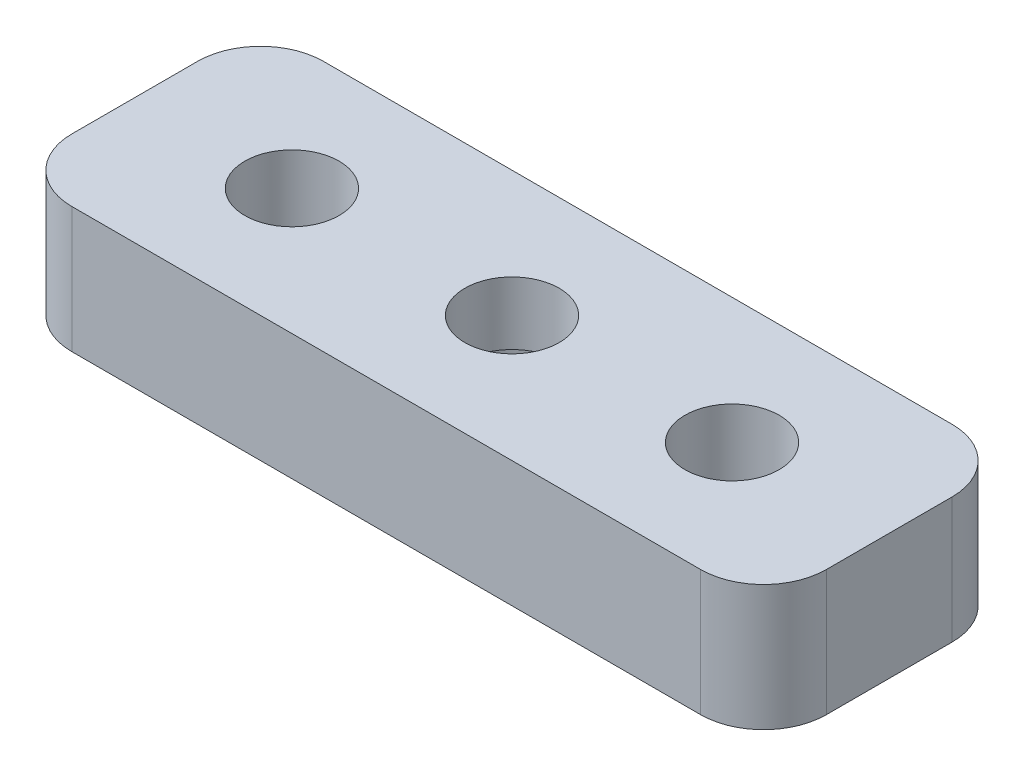
SolidWorks part; units mm, degrees
ref_plane "Front Plane" through (0, 0, 0) normal (0, 0, 1) x (1, 0, 0)
ref_plane "Top Plane" through (0, 0, 0) normal (0, 1, 0) x (1, 0, 0)
ref_plane "Right Plane" through (0, 0, 0) normal (1, 0, 0) x (0, 0, -1)
sketch "Sketch1" plane through (0, 0, 0) normal (0, 1, 0) x (1, 0, 0)
  line L0 (0, 4) -> (10, 4)
  line L1 (12, 2) -> (12, -2)
  line L2 (10, -4) -> (0, -4)
  line L3 (0, -4) -> (-10, -4)
  line L4 (-12, -2) -> (-12, 2)
  line L5 (-10, 4) -> (0, 4)
  line L6 (0, -2.2) -> (0, 2.2) construction
  circle A0 centre (0, 0) radius 4 construction
  circle A1 centre (0, 0) radius 1.5
  arc A2 (10, -4) -> (12, -2) centre (10, -2) ccw
  arc A3 (12, 2) -> (10, 4) centre (10, 2) ccw
  arc A4 (-10, -4) -> (-12, -2) centre (-10, -2) cw
  arc A5 (-10, 4) -> (-12, 2) centre (-10, 2) ccw
  circle A6 centre (0, 0) radius 2.5
  circle A7 centre (-7, 0) radius 1.5
  circle A8 centre (-7, 0) radius 2.5
  circle A9 centre (7, 0) radius 2.5
  circle A10 centre (7, 0) radius 1.5
  point P14 (12, 4)
  point P19 (-12, 4)
  dimension "D1" = 3
  dimension "D2" = 8
  dimension "D5" = 2
  dimension "D6" = 5
  dimension "D7" = 3
  dimension "D8" = 5
  dimension "D3" = 12
  dimension "D4" = 12
  dimension "D9" = 5
  dimension "D10" = 4
  dimension "D11" = 14
extrude "Boss-Extrude1" add sketch "Sketch1" along normal blind 4 contours L3 A4 L4 A5 L5 L0 A3 L1 A2 L2
extrude "Cut-Extrude1" cut sketch "Sketch1<3>" along normal up to next contours A1 | A7 | A10
sketch "Sketch1<3>" plane through (0, 0, 0) normal (0, 1, 0) x (1, 0, 0) same geometry as "Sketch1"
extrude "Cut-Extrude2" cut sketch "Sketch1<4>" along normal blind 2 contours A6
sketch "Sketch1<4>" plane through (0, 0, 0) normal (0, 1, 0) x (1, 0, 0) same geometry as "Sketch1"
